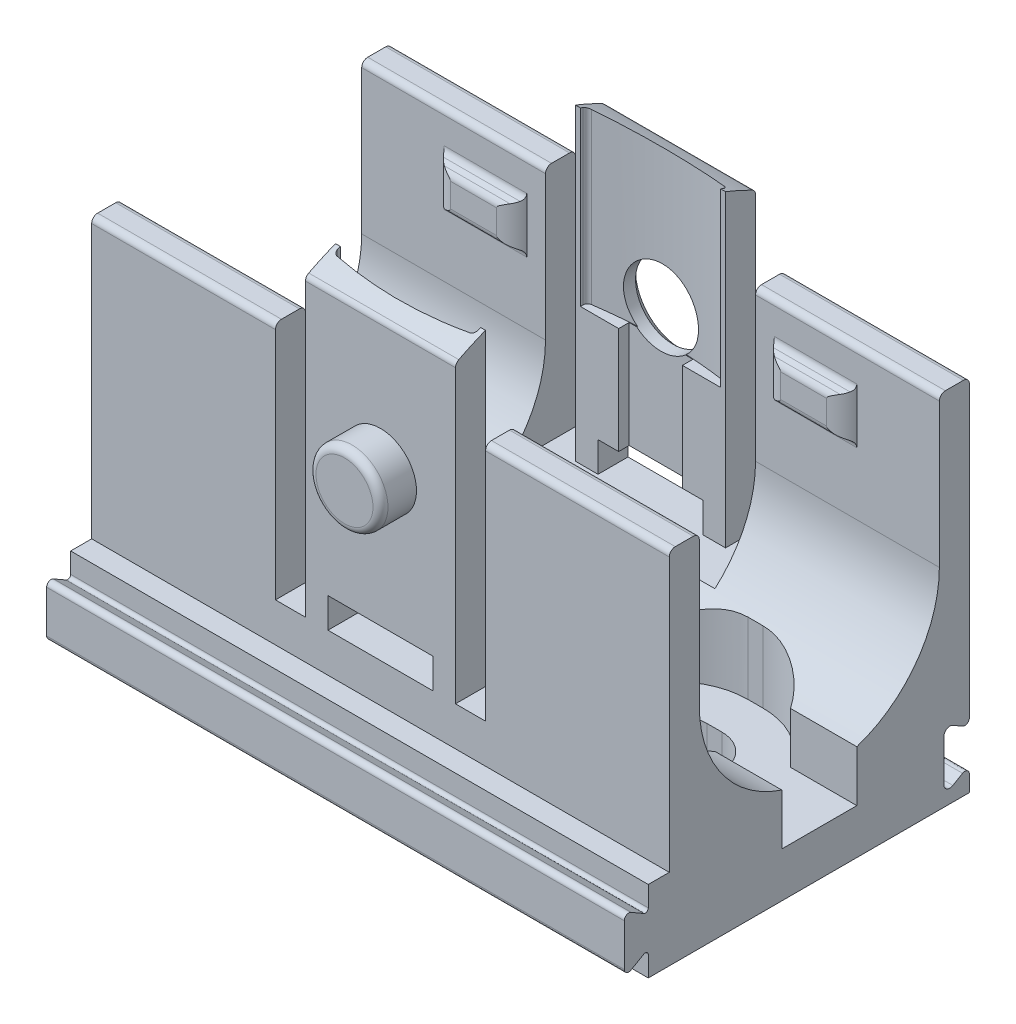
SolidWorks part; units mm, degrees
ref_plane "Front Plane" through (0, 0, 0) normal (0, 0, 1) x (1, 0, 0)
ref_plane "Top Plane" through (0, 0, 0) normal (0, 1, 0) x (1, 0, 0)
ref_plane "Right Plane" through (0, 0, 0) normal (1, 0, 0) x (0, 0, -1)
ref_plane "Plane1" through (0, 0, 0) normal (1, 0, 0) x (0, 0, -1)
sketch "Sketch1" plane through (0, 0, 0) normal (1, 0, 0) x (0, 0, -1)
  line L0 (-13, 4.1041) -> (-13, 1.2959)
  line L1 (-12.55, 1.036) -> (-11.7, 1.5268)
  line L2 (-11.4, 1.3536) -> (-11.4, 0)
  line L3 (-11.4, 0) -> (10, 0)
  line L4 (10, 0) -> (10, 1.0804)
  line L5 (9.55, 1.3402) -> (8.9, 0.9649)
  line L6 (8.3, 1.3113) -> (8.3, 4.0887)
  line L7 (8.9, 4.4351) -> (9.55, 4.0598)
  line L8 (10, 4.3196) -> (10, 23.6)
  line L9 (9.6, 24) -> (8.4, 24)
  line L10 (8, 23.6) -> (8, 14)
  line L11 (-8, 14) -> (-8, 23.6)
  line L12 (-8.4, 24) -> (-9.6, 24)
  line L13 (-10, 23.6) -> (-10, 5.4)
  line L14 (-10, 5.4) -> (-11.4, 5.4)
  line L15 (-11.4, 5.4) -> (-11.4, 4.0464)
  line L16 (-11.7, 3.8732) -> (-12.55, 4.364)
  arc A0 (-13, 1.2959) -> (-12.55, 1.036) centre (-12.7, 1.2959) ccw
  arc A1 (-11.7, 1.5268) -> (-11.4, 1.3536) centre (-11.6, 1.3536) cw
  arc A2 (10, 1.0804) -> (9.55, 1.3402) centre (9.7, 1.0804) ccw
  arc A3 (8.9, 0.9649) -> (8.3, 1.3113) centre (8.7, 1.3113) cw
  arc A4 (8.3, 4.0887) -> (8.9, 4.4351) centre (8.7, 4.0887) cw
  arc A5 (9.55, 4.0598) -> (10, 4.3196) centre (9.7, 4.3196) ccw
  arc A6 (10, 23.6) -> (9.6, 24) centre (9.6, 23.6) ccw
  arc A7 (8.4, 24) -> (8, 23.6) centre (8.4, 23.6) ccw
  arc A8 (8, 14) -> (-8, 14) centre (0, 14) cw
  arc A9 (-8, 23.6) -> (-8.4, 24) centre (-8.4, 23.6) ccw
  arc A10 (-9.6, 24) -> (-10, 23.6) centre (-9.6, 23.6) ccw
  arc A11 (-11.4, 4.0464) -> (-11.7, 3.8732) centre (-11.6, 4.0464) cw
  arc A12 (-12.55, 4.364) -> (-13, 4.1041) centre (-12.7, 4.1041) ccw
extrude "Boss-Extrude1" add sketch "Sketch1" against normal blind 19.25 and the other way blind 19.25
ref_plane "Plane2" through (0, 0, 0) normal (0, 0, 1) x (1, 0, 0)
sketch "Sketch2" plane through (0, 0, 0) normal (0, 0, 1) x (1, 0, 0)
  line L0 (-7, 33) -> (-7, 8)
  line L1 (-7, 8) -> (7, 8)
  line L2 (7, 8) -> (7, 33)
  line L3 (7, 33) -> (-7, 33)
extrude "Cut-Extrude1" cut sketch "Sketch2" against normal blind 12 and the other way blind 12
ref_plane "Plane3" through (0, 0, 0) normal (1, 0, 0) x (0, 0, -1)
sketch "Sketch3" plane through (0, 0, 0) normal (1, 0, 0) x (0, 0, -1)
  line L0 (8, 28.5639) -> (8, 8)
  line L1 (8, 8) -> (10, 8)
  line L2 (10, 8) -> (10, 27.4019)
  arc A0 (10, 27.4019) -> (9.7811, 27.7585) centre (9.6, 27.4019) ccw
  arc A1 (9.7811, 27.7585) -> (8, 28.5639) centre (0, 8.5) ccw
extrude "Boss-Extrude2" add sketch "Sketch3" against normal blind 5 and the other way blind 5
ref_plane "Plane4" through (0, 0, 0) normal (1, 0, 0) x (0, 0, -1)
sketch "Sketch4" plane through (0, 0, 0) normal (1, 0, 0) x (0, 0, -1)
  line L0 (-10, 27.4019) -> (-10, 8)
  line L1 (-10, 8) -> (-8, 8)
  line L2 (-8, 8) -> (-8, 28.5639)
  arc A0 (-8, 28.5639) -> (-9.7811, 27.7585) centre (0, 8.5) ccw
  arc A1 (-9.7811, 27.7585) -> (-10, 27.4019) centre (-9.6, 27.4019) ccw
extrude "Boss-Extrude3" add sketch "Sketch4" against normal blind 5 and the other way blind 5
ref_plane "Plane5" through (0, 0, 0) normal (0, 0, 1) x (1, 0, 0)
sketch "Sketch5" plane through (0, 0, 0) normal (0, 0, 1) x (1, 0, 0)
  line L0 (-3.5, 10) -> (-3.5, 8)
  line L1 (-3.5, 8) -> (3.5, 8)
  line L2 (3.5, 8) -> (3.5, 10)
  line L3 (3.5, 10) -> (-3.5, 10)
extrude "Cut-Extrude2" cut sketch "Sketch5" against normal blind 12 and the other way blind 12
ref_plane "Plane6" through (0, 0, 0) normal (1, 0, 0) x (0, 0, -1)
sketch "Sketch6" plane through (0, 0, 0) normal (1, 0, 0) x (0, 0, -1)
  line L0 (-12.4, 19) -> (-12.4, 20.9)
  line L1 (-11.9, 21.4) -> (-10, 21.4)
  line L2 (-10, 21.4) -> (-10, 19)
  line L3 (-10, 19) -> (-12.4, 19)
  line L4 (-10, 19) -> (-12.4, 19) construction
  arc A0 (-12.4, 20.9) -> (-11.9, 21.4) centre (-11.9, 20.9) cw
revolve "Revolve1" add sketch "Sketch6" angle 360 about L4 reverse direction yes
ref_plane "Plane7" through (0, 0, 0) normal (1, 0, 0) x (0, 0, -1)
sketch "Sketch7" plane through (0, 0, 0) normal (1, 0, 0) x (0, 0, -1)
  line L0 (8, 19) -> (8, 21.5)
  line L1 (8, 21.5) -> (9.5, 21.5)
  line L2 (9.5, 21.5) -> (10, 22)
  line L3 (10, 22) -> (10, 19)
  line L4 (10, 19) -> (8, 19)
  line L5 (10, 19) -> (8, 19) construction
revolve "Cut-Revolve1" cut sketch "Sketch7" angle 360 about L5 reverse direction yes
ref_plane "Plane8" through (8.25, 0, 0) normal (1, 0, 0) x (0, 0, -1)
sketch "Sketch8" plane through (8.25, 0, 0) normal (1, 0, 0) x (0, 0, -1)
  line L0 (7.2, 20.7994) -> (7.2, 19.2006)
  line L1 (7.45, 18.7675) -> (7.75, 18.5943)
  line L2 (8, 18.1613) -> (8, 21.8387)
  line L3 (7.75, 21.4057) -> (7.45, 21.2325)
  arc A0 (7.2, 19.2006) -> (7.45, 18.7675) centre (7.7, 19.2006) ccw
  arc A1 (7.75, 18.5943) -> (8, 18.1613) centre (7.5, 18.1613) cw
  arc A2 (8, 21.8387) -> (7.75, 21.4057) centre (7.5, 21.8387) cw
  arc A3 (7.45, 21.2325) -> (7.2, 20.7994) centre (7.7, 20.7994) ccw
extrude "Boss-Extrude4" add sketch "Sketch8" along normal blind 5.5
ref_plane "Plane9" through (8.25, 0, 0) normal (1, 0, 0) x (0, 0, -1)
sketch "Sketch9" plane through (8.25, 0, 0) normal (1, 0, 0) x (0, 0, -1)
  line L0 (-7.75, 18.5943) -> (-7.45, 18.7675)
  line L1 (-7.2, 19.2006) -> (-7.2, 20.7994)
  line L2 (-7.45, 21.2325) -> (-7.75, 21.4057)
  line L3 (-8, 21.8387) -> (-8, 18.1613)
  arc A0 (-8, 18.1613) -> (-7.75, 18.5943) centre (-7.5, 18.1613) cw
  arc A1 (-7.45, 18.7675) -> (-7.2, 19.2006) centre (-7.7, 19.2006) ccw
  arc A2 (-7.2, 20.7994) -> (-7.45, 21.2325) centre (-7.7, 20.7994) ccw
  arc A3 (-7.75, 21.4057) -> (-8, 21.8387) centre (-7.5, 21.8387) cw
extrude "Boss-Extrude5" add sketch "Sketch9" along normal blind 5.5
ref_plane "Plane10" through (-8.25, 0, 0) normal (1, 0, 0) x (0, 0, -1)
sketch "Sketch10" plane through (-8.25, 0, 0) normal (1, 0, 0) x (0, 0, -1)
  line L0 (7.2, 20.7994) -> (7.2, 19.2006)
  line L1 (7.45, 18.7675) -> (7.75, 18.5943)
  line L2 (8, 18.1613) -> (8, 21.8387)
  line L3 (7.75, 21.4057) -> (7.45, 21.2325)
  arc A0 (7.2, 19.2006) -> (7.45, 18.7675) centre (7.7, 19.2006) ccw
  arc A1 (7.75, 18.5943) -> (8, 18.1613) centre (7.5, 18.1613) cw
  arc A2 (8, 21.8387) -> (7.75, 21.4057) centre (7.5, 21.8387) cw
  arc A3 (7.45, 21.2325) -> (7.2, 20.7994) centre (7.7, 20.7994) ccw
extrude "Boss-Extrude6" add sketch "Sketch10" against normal blind 5.5
ref_plane "Plane11" through (-8.25, 0, 0) normal (1, 0, 0) x (0, 0, -1)
sketch "Sketch11" plane through (-8.25, 0, 0) normal (1, 0, 0) x (0, 0, -1)
  line L0 (-7.75, 18.5943) -> (-7.45, 18.7675)
  line L1 (-7.2, 19.2006) -> (-7.2, 20.7994)
  line L2 (-7.45, 21.2325) -> (-7.75, 21.4057)
  line L3 (-8, 21.8387) -> (-8, 18.1613)
  arc A0 (-8, 18.1613) -> (-7.75, 18.5943) centre (-7.5, 18.1613) cw
  arc A1 (-7.45, 18.7675) -> (-7.2, 19.2006) centre (-7.7, 19.2006) ccw
  arc A2 (-7.2, 20.7994) -> (-7.45, 21.2325) centre (-7.7, 20.7994) ccw
  arc A3 (-7.75, 21.4057) -> (-8, 21.8387) centre (-7.5, 21.8387) cw
extrude "Boss-Extrude7" add sketch "Sketch11" against normal blind 5.5
ref_plane "Plane12" through (0, 3, 0) normal (0, 1, 0) x (1, 0, 0)
sketch "Sketch12" plane through (0, 3, 0) normal (0, 1, 0) x (1, 0, 0)
  line L0 (9.5, -5) -> (10.5, -5)
  line L1 (14.8301, -2.5) -> (19.25, -2.5)
  line L2 (19.25, -2.5) -> (19.25, 2.5)
  line L3 (19.25, 2.5) -> (14.8301, 2.5)
  line L4 (10.5, 5) -> (9.5, 5)
  arc A0 (9.5, 5) -> (9.5, -5) centre (9.5, 0) ccw
  arc A1 (10.5, -5) -> (14.8301, -2.5) centre (10.5, 0) ccw
  arc A2 (14.8301, 2.5) -> (10.5, 5) centre (10.5, 0) ccw
extrude "Cut-Extrude3" cut sketch "Sketch12" along normal blind 7
ref_plane "Plane13" through (0, 3, 0) normal (0, 1, 0) x (1, 0, 0)
sketch "Sketch13" plane through (0, 3, 0) normal (0, 1, 0) x (1, 0, 0)
  line L0 (-19.25, -2.5) -> (-14.5826, -2.5)
  line L1 (-5, -0.5) -> (-5, 0.5)
  line L2 (-14.5826, 2.5) -> (-19.25, 2.5)
  line L3 (-19.25, 2.5) -> (-19.25, -2.5)
  arc A0 (-14.5826, -2.5) -> (-5, -0.5) centre (-10, -0.5) ccw
  arc A1 (-5, 0.5) -> (-14.5826, 2.5) centre (-10, 0.5) ccw
extrude "Cut-Extrude4" cut sketch "Sketch13" along normal blind 7
ref_plane "Plane14" through (0, 20, 0) normal (0, 1, 0) x (1, 0, 0)
sketch "Sketch14" plane through (0, 20, 0) normal (0, 1, 0) x (1, 0, 0)
  line L0 (8.25, 8) -> (8.25, 5)
  line L1 (8.25, 5) -> (13.75, 5)
  line L2 (13.75, 5) -> (13.75, 8)
  line L3 (12.5262, 7.2) -> (9.4738, 7.2)
  arc A0 (13.75, 8) -> (12.5262, 7.2) centre (12.2381, 8.9768) cw
  arc A1 (9.4738, 7.2) -> (8.25, 8) centre (9.7619, 8.9768) cw
extrude "Cut-Extrude5" cut sketch "Sketch14" against normal blind 2.5 and the other way blind 2.5
ref_plane "Plane15" through (0, 20, 0) normal (0, 1, 0) x (1, 0, 0)
sketch "Sketch15" plane through (0, 20, 0) normal (0, 1, 0) x (1, 0, 0)
  line L0 (-13.75, 8) -> (-13.75, 5)
  line L1 (-13.75, 5) -> (-8.25, 5)
  line L2 (-8.25, 5) -> (-8.25, 8)
  line L3 (-9.4738, 7.2) -> (-12.5262, 7.2)
  arc A0 (-8.25, 8) -> (-9.4738, 7.2) centre (-9.7619, 8.9768) cw
  arc A1 (-12.5262, 7.2) -> (-13.75, 8) centre (-12.2381, 8.9768) cw
extrude "Cut-Extrude6" cut sketch "Sketch15" against normal blind 2.5 and the other way blind 2.5
ref_plane "Plane16" through (0, 20, 0) normal (0, 1, 0) x (1, 0, 0)
sketch "Sketch16" plane through (0, 20, 0) normal (0, 1, 0) x (1, 0, 0)
  line L0 (9.4738, -7.2) -> (12.5262, -7.2)
  line L1 (13.75, -8) -> (13.75, -5)
  line L2 (13.75, -5) -> (8.25, -5)
  line L3 (8.25, -5) -> (8.25, -8)
  arc A0 (8.25, -8) -> (9.4738, -7.2) centre (9.7619, -8.9768) cw
  arc A1 (12.5262, -7.2) -> (13.75, -8) centre (12.2381, -8.9768) cw
extrude "Cut-Extrude7" cut sketch "Sketch16" against normal blind 2.5 and the other way blind 2.5
ref_plane "Plane17" through (0, 20, 0) normal (0, 1, 0) x (1, 0, 0)
sketch "Sketch17" plane through (0, 20, 0) normal (0, 1, 0) x (1, 0, 0)
  line L0 (-12.5262, -7.2) -> (-9.4738, -7.2)
  line L1 (-8.25, -8) -> (-8.25, -5)
  line L2 (-8.25, -5) -> (-13.75, -5)
  line L3 (-13.75, -5) -> (-13.75, -8)
  arc A0 (-13.75, -8) -> (-12.5262, -7.2) centre (-12.2381, -8.9768) cw
  arc A1 (-9.4738, -7.2) -> (-8.25, -8) centre (-9.7619, -8.9768) cw
extrude "Cut-Extrude8" cut sketch "Sketch17" against normal blind 2.5 and the other way blind 2.5
ref_plane "Plane18" through (0, 0, 0) normal (0, 1, 0) x (1, 0, 0)
sketch "Sketch18" plane through (0, 0, 0) normal (0, 1, 0) x (1, 0, 0)
  line L0 (-18.25, 6.8) -> (-18.25, -8.5)
  line L1 (-18.25, -8.5) -> (18.25, -8.5)
  line L2 (18.25, -8.5) -> (18.25, 6.8)
  line L3 (18.25, 6.8) -> (-18.25, 6.8)
extrude "Cut-Extrude9" cut sketch "Sketch18" along normal blind 1.5
ref_plane "Plane19" through (0, 17.1, 0) normal (0, 1, 0) x (1, 0, 0)
sketch "Sketch19" plane through (0, 17.1, 0) normal (0, 1, 0) x (1, 0, 0)
  line L0 (-4.675, 8.1782) -> (-4.675, -8.1782)
  line L1 (4.675, -8.1782) -> (4.675, 8.1782)
  arc A0 (-4.675, -8.1782) -> (-4.4189, -8.475) centre (-4.375, -8.1782) ccw
  arc A1 (-4.4189, -8.475) -> (4.4189, -8.475) centre (0, 21.4) ccw
  arc A2 (4.4189, -8.475) -> (4.675, -8.1782) centre (4.375, -8.1782) ccw
  arc A3 (4.675, 8.1782) -> (4.4189, 8.475) centre (4.375, 8.1782) ccw
  arc A4 (4.4189, 8.475) -> (-4.4189, 8.475) centre (0, -21.4) ccw
  arc A5 (-4.4189, 8.475) -> (-4.675, 8.1782) centre (-4.375, 8.1782) ccw
extrude "Cut-Extrude10" cut sketch "Sketch19" along normal blind 15
ref_plane "Plane20" through (0, 17.1, 0) normal (0, 1, 0) x (1, 0, 0)
sketch "Sketch20" plane through (0, 17.1, 0) normal (0, 1, 0) x (1, 0, 0)
  line L0 (-2.125, -8.7) -> (2.125, -8.7)
  line L1 (2.125, -8.7) -> (2.125, 8.7)
  line L2 (2.125, 8.7) -> (-2.125, 8.7)
  line L3 (-2.125, 8.7) -> (-2.125, -8.7)
extrude "Cut-Extrude11" cut sketch "Sketch20" against normal blind 8
ref_plane "Plane21" through (0, 5, 0) normal (0, 1, 0) x (1, 0, 0)
sketch "Sketch21" plane through (0, 5, 0) normal (0, 1, 0) x (1, 0, 0)
  line L0 (-1.125, -6.25) -> (1.125, -6.25)
  line L1 (2.125, -5.25) -> (2.125, 5.25)
  line L2 (1.125, 6.25) -> (-1.125, 6.25)
  line L3 (-2.125, 5.25) -> (-2.125, -5.25)
  arc A0 (-2.125, -5.25) -> (-1.125, -6.25) centre (-1.125, -5.25) ccw
  arc A1 (1.125, -6.25) -> (2.125, -5.25) centre (1.125, -5.25) ccw
  arc A2 (2.125, 5.25) -> (1.125, 6.25) centre (1.125, 5.25) ccw
  arc A3 (-1.125, 6.25) -> (-2.125, 5.25) centre (-1.125, 5.25) ccw
extrude "Cut-Extrude12" cut sketch "Sketch21" along normal blind 7
ref_plane "Plane22" through (0, 0, 0) normal (0, 1, 0) x (1, 0, 0)
sketch "Sketch22" plane through (0, 0, 0) normal (0, 1, 0) x (1, 0, 0)
  line L0 (9.5, -2.25) -> (10.5, -2.25)
  line L1 (10.5, 2.25) -> (9.5, 2.25)
  arc A0 (9.5, 2.25) -> (9.5, -2.25) centre (9.5, 0) ccw
  arc A1 (10.5, -2.25) -> (10.5, 2.25) centre (10.5, 0) ccw
extrude "Cut-Extrude13" cut sketch "Sketch22" along normal blind 7
ref_plane "Plane23" through (0, 0, 0) normal (0, 1, 0) x (1, 0, 0)
sketch "Sketch23" plane through (0, 0, 0) normal (0, 1, 0) x (1, 0, 0)
  line L0 (9.5, -3.75) -> (10.5, -3.75)
  line L1 (10.5, 3.75) -> (9.5, 3.75)
  line L2 (9.5, -2.25) -> (10.5, -2.25)
  line L3 (10.5, 2.25) -> (9.5, 2.25)
  arc A0 (9.5, 3.75) -> (9.5, -3.75) centre (9.5, 0) ccw
  arc A1 (10.5, -3.75) -> (10.5, 3.75) centre (10.5, 0) ccw
  arc A2 (9.5, 2.25) -> (9.5, -2.25) centre (9.5, 0) ccw
  arc A3 (10.5, -2.25) -> (10.5, 2.25) centre (10.5, 0) ccw
extrude "Boss-Extrude8" add sketch "Sketch23" along normal blind 1.5
ref_plane "Plane24" through (0, 0, 0) normal (0, 1, 0) x (1, 0, 0)
sketch "Sketch24" plane through (0, 0, 0) normal (0, 1, 0) x (1, 0, 0)
  line L0 (-12.25, 0.5) -> (-12.25, -0.5)
  line L1 (-7.75, -0.5) -> (-7.75, 0.5)
  arc A0 (-12.25, -0.5) -> (-7.75, -0.5) centre (-10, -0.5) ccw
  arc A1 (-7.75, 0.5) -> (-12.25, 0.5) centre (-10, 0.5) ccw
extrude "Cut-Extrude14" cut sketch "Sketch24" along normal blind 4
ref_plane "Plane25" through (0, 0, 0) normal (0, 1, 0) x (1, 0, 0)
sketch "Sketch25" plane through (0, 0, 0) normal (0, 1, 0) x (1, 0, 0)
  line L0 (-6.25, -0.5) -> (-6.25, 0.5)
  line L1 (-13.75, 0.5) -> (-13.75, -0.5)
  line L2 (-7.75, -0.5) -> (-7.75, 0.5)
  line L3 (-12.25, 0.5) -> (-12.25, -0.5)
  arc A0 (-13.75, -0.5) -> (-6.25, -0.5) centre (-10, -0.5) ccw
  arc A1 (-6.25, 0.5) -> (-13.75, 0.5) centre (-10, 0.5) ccw
  arc A2 (-12.25, -0.5) -> (-7.75, -0.5) centre (-10, -0.5) ccw
  arc A3 (-7.75, 0.5) -> (-12.25, 0.5) centre (-10, 0.5) ccw
extrude "Boss-Extrude9" add sketch "Sketch25" along normal blind 1.5
